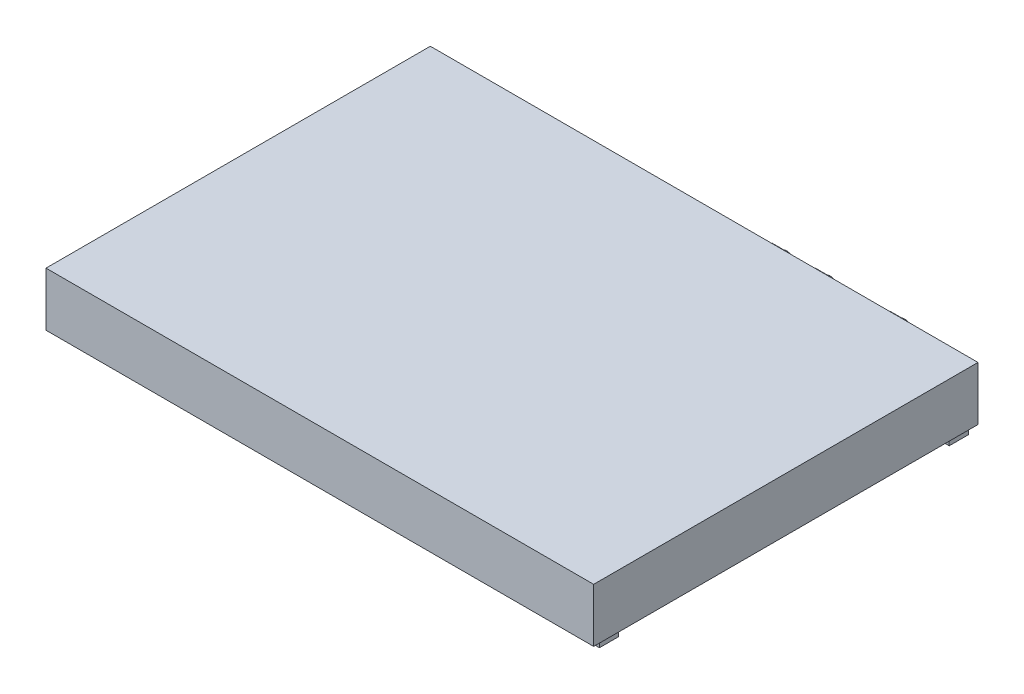
SolidWorks part; units mm, degrees
material "AISI 304"
ref_plane "Ebene vorne" through (0, 0, 0) normal (0, 0, 1) x (1, 0, 0)
ref_plane "Ebene oben" through (0, 0, 0) normal (0, 1, 0) x (1, 0, 0)
ref_plane "Ebene rechts" through (0, 0, 0) normal (1, 0, 0) x (0, 0, -1)
sketch "Skizze1" plane through (0, 0, 0) normal (1, 0, 0) x (0, 0, -1)
  line L1 (-100, -14) -> (100, -14)
  line L2 (-100, -14) -> (-100, 14)
  line L3 (-100, 14) -> (100, 14)
  line L4 (100, -14) -> (100, 14)
  line L5 (-100, -14) -> (100, 14) construction
  line L6 (-100, 14) -> (100, -14) construction
  point P0 (0, 0)
  dimension "D1" = 28
  dimension "D2" = 200
extrude "Aufsatz-Linear austragen1" add sketch "Skizze1" along normal mid plane 285
sketch "Skizze2" plane through (0, 0, -100) normal (0, 0, -1) x (-1, 0, 0)
  line L0 (-142.5, 14) -> (142.5, 14) construction
  line L1 (123, 11.75) -> (138, 11.75)
  line L2 (123, 11.75) -> (123, -8.95)
  line L3 (123, -8.95) -> (138, -8.95)
  line L4 (138, 11.75) -> (138, -8.95)
  line L5 (142.5, -14) -> (142.5, 14) construction
  dimension "D1" = 15
  dimension "D2" = 20.7
  dimension "D3" = 2.25
  dimension "D4" = 4.5
extrude "Aufsatz-Linear austragen2" add sketch "Skizze2" along normal blind 2
ref_plane "Ebene1" through (-130.5, 0, 0) normal (-1, 0, 0) x (0, 0, 1)
sketch "Skizze3" plane through (-130.5, 0, 0) normal (-1, 0, 0) x (0, 0, 1)
  line L0 (-102, 9.25) -> (-106.5, 6.6519)
  line L1 (-106.5, 6.6519) -> (-102, -6.95)
  line L2 (-102, -6.95) -> (-102, 9.25)
  line L3 (-102, 11.75) -> (-102, -8.95) construction
  line L5 (-102, 11.75) -> (-100, 11.75) construction
  dimension "D1" = 2
  dimension "D2" = 2.5
  dimension "D3" = 4.5
  dimension "D4" = 60
extrude "Aufsatz-Linear austragen3" add sketch "Skizze3" along normal mid plane 10
sketch "Skizze4" plane through (0, 0, -100) normal (0, 0, -1) x (-1, 0, 0)
  line L0 (-142.5, 2) -> (-96.5, 2) construction
  line L1 (-142.5, -14) -> (-142.5, 14) construction
  line L2 (-96.5, 2) -> (-57.5, 2) construction
  line L3 (-57.5, 2) -> (-35, 2) construction
  line L4 (-142.5, 14) -> (142.5, 14) construction
  point P0 (-96.5, 2)
  point P1 (-57.5, 2)
  point P2 (-35, 2)
  dimension "D1" = 46
  dimension "D2" = 85
  dimension "D3" = 22.5
  dimension "D4" = 12
sketch "Skizze5" plane through (0, 0, -100) normal (0, 0, -1) x (-1, 0, 0)
  line L1 (-100.8301, -5.5) -> (-92.1699, -5.5)
  line L2 (-92.1699, -5.5) -> (-87.8397, 2)
  line L3 (-87.8397, 2) -> (-92.1699, 9.5)
  line L4 (-92.1699, 9.5) -> (-100.8301, 9.5)
  line L5 (-100.8301, 9.5) -> (-105.1603, 2)
  line L6 (-105.1603, 2) -> (-100.8301, -5.5)
  circle A0 centre (-96.5, 2) radius 7.5 construction
  dimension "D1" = 15
extrude "Aufsatz-Linear austragen4" add sketch "Skizze5" along normal blind 4.7
sketch "Skizze6" plane through (0, 0, -104.7) normal (0, 0, -1) x (-1, 0, 0)
  circle A0 centre (-96.5, 2) radius 4.5
  dimension "D1" = 9
extrude "Aufsatz-Linear austragen5" add sketch "Skizze6" along normal blind 3.3
sketch "Skizze7" plane through (0, 0, -108) normal (0, 0, -1) x (-1, 0, 0)
  circle A0 centre (-96.5, 2) radius 3.25
  dimension "D1" = 6.5
extrude "Schnitt-Linear austragen1" [suppressed] cut sketch "Skizze7" against normal blind 44
pattern_sketch "Skizzen-Muster1" of "Aufsatz-Linear austragen5", "Aufsatz-Linear austragen4", "Schnitt-Linear austragen1" driven by "Skizze4"
sketch "Skizze8" plane through (0, -14, 0) normal (0, -1, 0) x (1, 0, 0)
  line L0 (142.5, 100) -> (142.5, -100) construction
  line L1 (141.5, -96) -> (131.5, -96)
  line L2 (141.5, -96) -> (141.5, -86)
  line L3 (141.5, -86) -> (131.5, -86)
  line L4 (131.5, -96) -> (131.5, -86)
  line L5 (142.5, -100) -> (-142.5, -100) construction
  dimension "D1" = 1
  dimension "D2" = 4
  dimension "D3" = 10
extrude "Aufsatz-Linear austragen6" add sketch "Skizze8" along normal blind 3.1
mirror "Spiegeln1" about plane through (0, 0, 0) normal (1, 0, 0) of "Aufsatz-Linear austragen6"
mirror "Spiegeln2" about plane through (0, 0, 0) normal (0, 0, 1) of "Spiegeln1"
